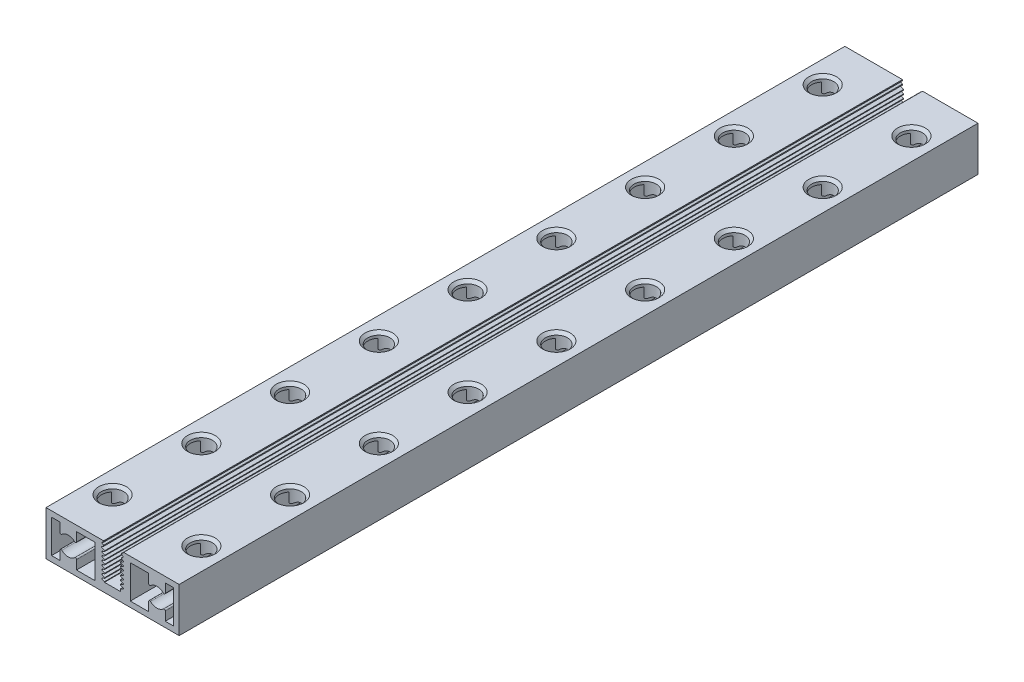
SolidWorks part; units mm, degrees
ref_plane "Front Plane" through (0, 0, 0) normal (0, 0, 1) x (1, 0, 0)
ref_plane "Top Plane" through (0, 0, 0) normal (0, 1, 0) x (1, 0, 0)
ref_plane "Right Plane" through (0, 0, 0) normal (1, 0, 0) x (0, 0, -1)
ref_plane "Plane1" through (0, 8, 0) normal (0, 1, 0) x (1, 0, 0)
sketch "Sketch1" plane through (0, 8, 0) normal (0, 1, 0) x (1, 0, 0)
  line L0 (12, 0) -> (-12, 0)
  line L1 (-12, 0) -> (-12, -144)
  line L2 (-12, -144) -> (12, -144)
  line L3 (12, -144) -> (12, 0)
extrude "Boss-Extrude1" add sketch "Sketch1" against normal blind 8
sketch "Sketch2" plane through (0, 0, 0) normal (0, 0, -1) x (-1, 0, 0)
  line L0 (1.62, 8) -> (-2, 8)
  line L1 (-2, 8) -> (-2, 7.88)
  line L2 (-2, 7.88) -> (-1.4684, 7.5731)
  line L3 (-1.4684, 7.5731) -> (-2.0747, 7.2231)
  line L4 (-2.0747, 7.2231) -> (-1.4684, 6.8731)
  line L5 (-1.4684, 6.8731) -> (-2.0878, 6.5155)
  line L6 (-2.0878, 6.5155) -> (-1.2404, 6.1731)
  line L7 (-1.2404, 6.1731) -> (-2.1067, 5.8231)
  line L8 (-2.1067, 5.8231) -> (-1.2404, 5.4731)
  line L9 (-1.2404, 5.4731) -> (-2.1067, 5.1231)
  line L10 (-2.1067, 5.1231) -> (-1.2404, 4.7731)
  line L11 (-1.2404, 4.7731) -> (-2.1067, 4.4231)
  line L12 (-2.1067, 4.4231) -> (-1.2404, 4.0731)
  line L13 (-1.2404, 4.0731) -> (-2.1067, 3.7231)
  line L14 (-2.1067, 3.7231) -> (-1.2404, 3.3731)
  line L15 (-1.2404, 3.3731) -> (-2.1067, 3.0231)
  line L16 (-2.1067, 3.0231) -> (-1.2404, 2.6731)
  line L17 (-1.2404, 2.6731) -> (-2.1067, 2.3231)
  line L18 (-2.1067, 2.3231) -> (-1.46, 2.0618)
  line L19 (-1.46, 2.0618) -> (-1.46, 1.6)
  line L20 (-1.46, 1.6) -> (1.46, 1.6)
  line L21 (1.46, 1.6) -> (1.46, 1.7012)
  line L22 (1.46, 1.7012) -> (2.1067, 1.9625)
  line L23 (2.1067, 1.9625) -> (1.2404, 2.3125)
  line L24 (1.2404, 2.3125) -> (2.1067, 2.6625)
  line L25 (2.1067, 2.6625) -> (1.2404, 3.0125)
  line L26 (1.2404, 3.0125) -> (2.1067, 3.3625)
  line L27 (2.1067, 3.3625) -> (1.2404, 3.7125)
  line L28 (1.2404, 3.7125) -> (2.1067, 4.0625)
  line L29 (2.1067, 4.0625) -> (1.2404, 4.4125)
  line L30 (1.2404, 4.4125) -> (2.1067, 4.7625)
  line L31 (2.1067, 4.7625) -> (1.2404, 5.1125)
  line L32 (1.2404, 5.1125) -> (2.1067, 5.4625)
  line L33 (2.1067, 5.4625) -> (1.2404, 5.8125)
  line L34 (1.2404, 5.8125) -> (2.1067, 6.1625)
  line L35 (2.1067, 6.1625) -> (1.2404, 6.5125)
  line L36 (1.2404, 6.5125) -> (2.0878, 6.8549)
  line L37 (2.0878, 6.8549) -> (1.4684, 7.2125)
  line L38 (1.4684, 7.2125) -> (2.0747, 7.5625)
  line L39 (2.0747, 7.5625) -> (1.62, 7.825)
  line L40 (1.62, 7.825) -> (1.62, 8)
extrude "Cut-Extrude1" cut sketch "Sketch2" against normal through all
sketch "Sketch3" plane through (0, 0, 144) normal (0, 0, 1) x (1, 0, 0)
  line L0 (-6.5, 1) -> (-3.2, 1)
  line L1 (-3.2, 1) -> (-3.2, 7)
  line L2 (-3.2, 7) -> (-6.5, 7)
  line L3 (-6.5, 7) -> (-6.5, 5.3856)
  line L4 (-9.5, 5.3856) -> (-9.5, 7)
  line L5 (-9.5, 7) -> (-11, 7)
  line L6 (-11, 7) -> (-11, 1)
  line L7 (-11, 1) -> (-9.5, 1)
  line L8 (-9.5, 1) -> (-9.5, 2.6144)
  line L9 (-6.5, 2.6144) -> (-6.5, 1)
  arc A0 (-6.5, 5.3856) -> (-6.8368, 5.2398) centre (-6.7, 5.3856) cw
  arc A1 (-6.8368, 5.2398) -> (-9.1632, 5.2398) centre (-8, 4) ccw
  arc A2 (-9.1632, 5.2398) -> (-9.5, 5.3856) centre (-9.3, 5.3856) cw
  arc A3 (-9.5, 2.6144) -> (-9.1632, 2.7602) centre (-9.3, 2.6144) cw
  arc A4 (-9.1632, 2.7602) -> (-6.8368, 2.7602) centre (-8, 4) ccw
  arc A5 (-6.8368, 2.7602) -> (-6.5, 2.6144) centre (-6.7, 2.6144) cw
extrude "Cut-Extrude2" cut sketch "Sketch3" against normal through all
sketch "Sketch4" plane through (0, 0, 0) normal (0, 0, -1) x (-1, 0, 0)
  line L0 (-6.5, 2.6144) -> (-6.5, 1)
  line L1 (-6.5, 1) -> (-3.2, 1)
  line L2 (-3.2, 1) -> (-3.2, 7)
  line L3 (-3.2, 7) -> (-6.5, 7)
  line L4 (-6.5, 7) -> (-6.5, 5.3856)
  line L5 (-9.5, 5.3856) -> (-9.5, 7)
  line L6 (-9.5, 7) -> (-11, 7)
  line L7 (-11, 7) -> (-11, 1)
  line L8 (-11, 1) -> (-9.5, 1)
  line L9 (-9.5, 1) -> (-9.5, 2.6144)
  arc A0 (-6.5, 5.3856) -> (-6.8368, 5.2398) centre (-6.7, 5.3856) cw
  arc A1 (-6.8368, 5.2398) -> (-9.1632, 5.2398) centre (-8, 4) ccw
  arc A2 (-9.1632, 5.2398) -> (-9.5, 5.3856) centre (-9.3, 5.3856) cw
  arc A3 (-9.5, 2.6144) -> (-9.1632, 2.7602) centre (-9.3, 2.6144) cw
  arc A4 (-9.1632, 2.7602) -> (-6.8368, 2.7602) centre (-8, 4) ccw
  arc A5 (-6.8368, 2.7602) -> (-6.5, 2.6144) centre (-6.7, 2.6144) cw
extrude "Cut-Extrude3" cut sketch "Sketch4" against normal through all
hole_wizard "Ø4.0 (4) Diameter Hole1" positions "Sketch6" profile "Sketch5" hole size "Ø4.0" standard "ANSI Metric"
sketch "Sketch6" plane through (0, 8, 0) normal (0, 1, 0) x (1, 0, 0)
  point P0 (8, -24)
  point P1 (8, -40)
  point P2 (8, -8)
  point P3 (8, -56)
  point P4 (8, -72)
  point P5 (8, -88)
  point P6 (8, -104)
  point P7 (8, -120)
  point P8 (8, -136)
  point P9 (-8, -8)
  point P10 (-8, -24)
  point P11 (-8, -40)
  point P12 (-8, -56)
  point P13 (-8, -72)
  point P14 (-8, -88)
  point P15 (-8, -104)
  point P16 (-8, -120)
  point P17 (-8, -136)
sketch "Sketch5" plane through (8, 8, 24) normal (1, 0, 0) x (0, 0, 1)
  line L0 (0, 0) -> (0, 10.8144)
  line L1 (0, 10.8144) -> (2, 10.8144)
  line L2 (2, 10.8144) -> (2, 0)
  line L5 (2, 0) -> (0, 0)
  line L10 (0, 10.8144) -> (-2, 10.8144) construction
  line L11 (0, -6.35) -> (0, 107.95) construction
  dimension "Hole Dia." = 4
  dimension "Hole Depth" = 10.8144
  dimension "Drill Angle" = 180
chamfer "Chamfer1" distance 0.5 angle 45 36 edges at (-8, 0, 106) (8, 8, 90) (-8, 8, 106) (-8, 0, 42) (-8, 8, 42) (8, 8, 26) (-8, 0, 10) (-8, 0, 74) (-8, 0, 138) (-8, 8, 74) (-8, 8, 138) (8, 8, 58) (8, 8, 122) (-8, 0, 26) (-8, 0, 58) (-8, 0, 90) (-8, 0, 122) (-8, 8, 58) (-8, 8, 90) (-8, 8, 122) (8, 8, 10) (8, 8, 42) (8, 8, 74) (8, 8, 106) (8, 8, 138) (8, 0, 10) (8, 0, 26) (8, 0, 42) (8, 0, 58) (8, 0, 74) (8, 0, 90) (8, 0, 106) (8, 0, 122) (8, 0, 138) (-8, 8, 10) (-8, 8, 26)
chamfer "Chamfer2" distance 0.169 angle 68 26 edges at (-1.2404, 5.1125, 72) (2.1067, 5.1231, 72) (1.2404, 4.7731, 72) (-1.2404, 4.4125, 72) (-2.1067, 5.4625, 72) (1.2404, 5.4731, 72) (2.1067, 4.4231, 72) (-2.1067, 4.0625, 72) (-1.2404, 5.8125, 72) (2.1067, 5.8231, 72) (1.2404, 4.0731, 72) (-1.2404, 3.7125, 72) (-2.1067, 6.1625, 72) (1.2404, 6.1731, 72) (2.1067, 3.7231, 72) (-2.1067, 4.7625, 72) (-2.1067, 3.3625, 72) (-1.2404, 6.5125, 72) (1.2404, 3.3731, 72) (-1.2404, 3.0125, 72) (2.1067, 3.0231, 72) (-2.1067, 2.6625, 72) (1.2404, 2.6731, 72) (-1.2404, 2.3125, 72) (2.1067, 2.3231, 72) (-2.1067, 1.9625, 72) first distance on face at (-1.6736, 4.9375, 72) first distance on face at (1.6736, 4.9481, 72) first distance on face at (1.6736, 4.5981, 72) first distance on face at (-1.6736, 4.2375, 72) first distance on face at (-1.6736, 5.6375, 72) first distance on face at (1.6736, 5.2981, 72) first distance on face at (1.6736, 4.2481, 72) first distance on face at (1.6736, 5.6481, 72) first distance on face at (1.6736, 3.8981, 72) first distance on face at (-1.6736, 3.5375, 72) first distance on face at (-1.6736, 6.3375, 72) first distance on face at (1.6736, 5.9981, 72) first distance on face at (1.6736, 3.5481, 72) first distance on face at (1.6736, 3.1981, 72) first distance on face at (-1.6736, 2.8375, 72) first distance on face at (1.6736, 2.8481, 72) first distance on face at (1.6736, 2.4981, 72) first distance on face at (-1.6736, 2.1375, 72) first distance on face at (1.7833, 2.1925, 72)
chamfer "Chamfer3" distance 0.175 angle 60 5 edges at (1.4684, 6.8731, 72) (-1.4684, 7.2125, 72) (2.0747, 7.2231, 72) (-2.0747, 7.5625, 72) (1.4684, 7.5731, 72) first distance on face at (1.7781, 6.6943, 72) first distance on face at (-1.7716, 7.3875, 72) first distance on face at (1.7716, 7.3981, 72) first distance on face at (-1.8473, 7.6938, 72)
chamfer "Chamfer4" distance 0.1014 angle 60 1 edges at (-2.0878, 6.8549, 72) first distance on face at (-1.8539, 6.9899, 72)
chamfer "Chamfer5" distance 0.1487 angle 68 1 edges at (2.0878, 6.5155, 72) first distance on face at (1.7425, 6.376, 72)
